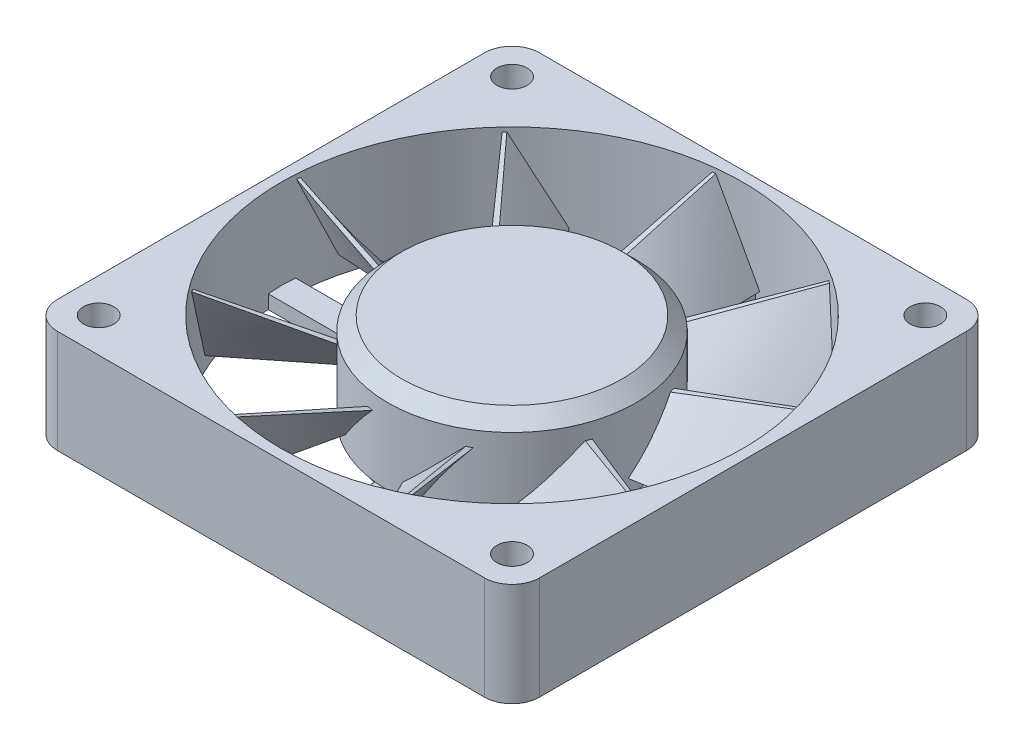
SolidWorks part; units mm, degrees
ref_plane "Front Plane" through (0, 0, 0) normal (0, 0, 1) x (1, 0, 0)
ref_plane "Top Plane" through (0, 0, 0) normal (0, 1, 0) x (1, 0, 0)
ref_plane "Right Plane" through (0, 0, 0) normal (1, 0, 0) x (0, 0, -1)
sketch "Sketch1" plane through (0, 0, 0) normal (0, 1, 0) x (1, 0, 0)
  line L1 (-31, 35) -> (31, 35)
  line L2 (-35, 31) -> (-35, -31)
  line L3 (-31, -35) -> (31, -35)
  line L4 (35, 31) -> (35, -31)
  circle A0 centre (0, 0) radius 33.5
  circle A1 centre (-30, 30) radius 2.2
  circle A2 centre (30, 30) radius 2.2
  circle A3 centre (30, -30) radius 2.2
  circle A4 centre (-30, -30) radius 2.2
  arc A5 (31, -35) -> (35, -31) centre (31, -31) ccw
  arc A6 (31, 35) -> (35, 31) centre (31, 31) cw
  arc A7 (-31, 35) -> (-35, 31) centre (-31, 31) ccw
  arc A8 (-35, -31) -> (-31, -35) centre (-31, -31) ccw
  point P17 (35, -35)
  point P20 (35, 35)
  point P23 (-35, 35)
  dimension "D1" = 67
  dimension "D2" = 30
  dimension "D8" = 4
  dimension "D3" = 30
  dimension "D4" = 35
  dimension "D5" = 35
  dimension "D6" = 70
  dimension "D7" = 70
extrude "Boss-Extrude1" add sketch "Sketch1" along normal blind 15
sketch "Sketch2" plane through (0, 0, 0) normal (0, 1, 0) x (1, 0, 0)
  line L0 (-1.9855, 33.3801) -> (0, 33.5)
  line L1 (0, 33.5) -> (1.9855, 33.3801)
  line L2 (33.3801, 1.9855) -> (33.5, 0)
  line L3 (33.5, 0) -> (33.3801, -1.9855)
  line L4 (-16.3801, 1.9855) -> (-33.3801, 1.9855)
  line L5 (-16.3801, -1.9855) -> (-33.3801, -1.9855)
  line L6 (1.9855, 16.3801) -> (1.9855, 33.3801)
  line L7 (16.3801, -1.9855) -> (33.3801, -1.9855)
  line L8 (-1.9855, -16.3801) -> (-1.9855, -33.3801)
  line L9 (-1.9855, 16.3801) -> (-1.9855, 33.3801)
  line L10 (16.3801, 1.9855) -> (33.3801, 1.9855)
  line L11 (1.9855, -16.3801) -> (1.9855, -33.3801)
  line L12 (-1.9855, -33.3801) -> (0, -33.5)
  line L13 (0, -33.5) -> (1.9855, -33.3801)
  line L14 (-33.3801, -1.9855) -> (-33.5, 0)
  line L15 (-33.5, 0) -> (-33.3801, 1.9855)
  arc A0 (-16.3801, -1.9855) -> (-1.9855, -16.3801) centre (0, 0) ccw
  circle A1 centre (0, 0) radius 33.5 construction
  arc A2 (-1.9855, 16.3801) -> (-16.3801, 1.9855) centre (0, 0) ccw
  arc A3 (16.3801, 1.9855) -> (1.9855, 16.3801) centre (0, 0) ccw
  arc A4 (1.9855, -16.3801) -> (16.3801, -1.9855) centre (0, 0) ccw
extrude "Boss-Extrude2" add sketch "Sketch2" along normal blind 2 separate body
sketch "Sketch3" plane through (0, 2, 0) normal (0, 1, 0) x (1, 0, 0)
  circle A0 centre (0, 0) radius 18
  dimension "D1" = 36
extrude "Boss-Extrude3" add sketch "Sketch3" along normal blind 13
chamfer "Chamfer1" distance 2 angle 45 1 edges at (0, 15, 18)
ref_plane "Plane3" through (0, 0, -33) normal (0, 0, -1) x (-1, 0, 0)
ref_plane "Plane4" through (0, 0, -17) normal (0, 0, -1) x (-1, 0, 0)
sketch "Sketch7" plane through (0, 0, -17) normal (0, 0, -1) x (-1, 0, 0)
  line L1 (3.0038, 10.6159) -> (3.8061, 10.6159)
  line L2 (3.0038, 10.6159) -> (-4.2368, 4.052)
  line L3 (-4.2368, 4.052) -> (-2.1593, 4.052)
  line L4 (3.8061, 10.6159) -> (-2.1593, 4.052)
sketch "Sketch8" plane through (0, 0, -33) normal (0, 0, -1) x (-1, 0, 0)
  line L1 (-2.9643, 2.9629) -> (-1.3827, 2.9629)
  line L2 (-2.9643, 2.9629) -> (3.4194, 14.5929)
  line L3 (3.4194, 14.5929) -> (3.9051, 14.5929)
  line L4 (-1.3827, 2.9629) -> (3.9051, 14.5929)
loft "Loft2" add profiles "Sketch8", "Sketch7" connector at (-3.9051, 14.5929, -33) connector at (-3.8061, 10.6159, -17)
pattern_circular "CirPattern33" count 9 over 360 about axis through (0, 15, 0) along (0, -1, 0) of "Loft2"
